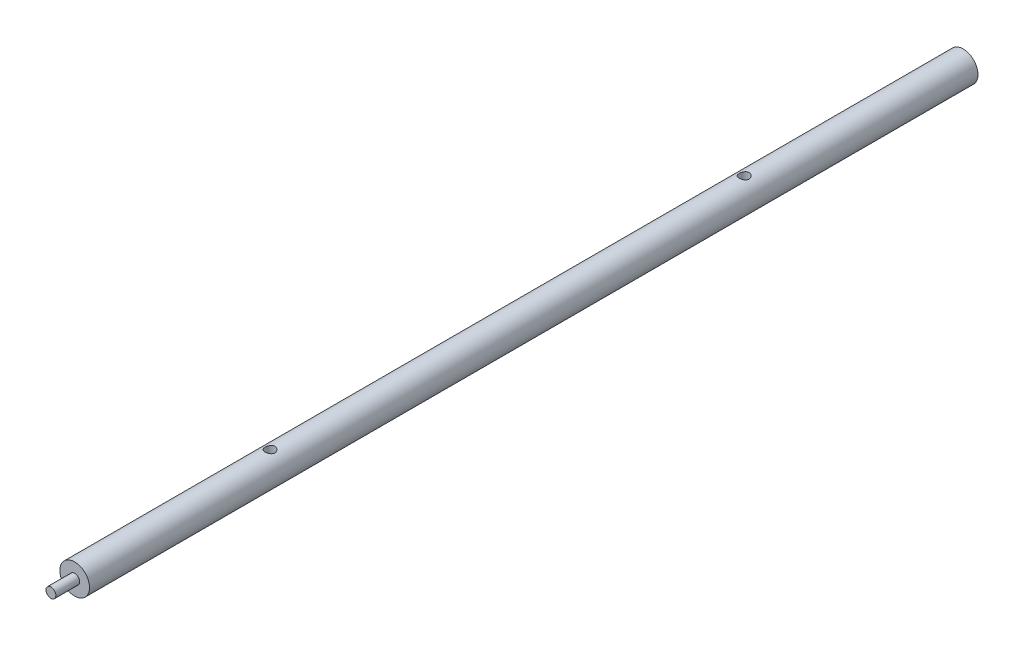
SolidWorks part; units mm, degrees
material "Plain Carbon Steel"
ref_plane "Front Plane" through (0, 0, 0) normal (0, 0, 1) x (1, 0, 0)
ref_plane "Top Plane" through (0, 0, 0) normal (0, 1, 0) x (1, 0, 0)
ref_plane "Right Plane" through (0, 0, 0) normal (1, 0, 0) x (0, 0, -1)
sketch "Sketch1" plane through (0, 0, 0) normal (0, 0, 1) x (1, 0, 0)
  circle A0 centre (0, 0) radius 9.525
  dimension "D1" = 19.05
extrude "Boss-Extrude1" add sketch "Sketch1" along normal blind 586.105
sketch3d "3DSketch1" plane through (0, 0, 0) normal (0, 0, 1) x (1, 0, 0)
ref_axis "Axis1" through (0, 0, 586.105) along (0, 0, -1)
ref_plane "Plane1" through (0, -9.525, 0) normal (0, 1, 0) x (1, 0, 0)
sketch "Sketch3" plane through (0, -9.525, 0) normal (0, 1, 0) x (1, 0, 0)
  line L0 (0, -586.105) -> (0, 0) construction
  line L1 (9.525, 0) -> (-9.525, 0) construction
  line L2 (-9.525, -586.105) -> (9.525, -586.105) construction
  circle A0 centre (0, -445.389) radius 3.175
  circle A1 centre (0, -140.716) radius 3.175
  dimension "D1" = 0
  dimension "D2" = 0
  dimension "D3" = 6.35
  dimension "D4" = 140.716
  dimension "D5" = 6.35
  dimension "D6" = 140.716
extrude "Cut-Extrude2" cut sketch "Sketch3" along normal up to next
sketch "Sketch5" plane through (0, -9.525, 0) normal (0, 1, 0) x (1, 0, 0)
  line L0 (0, -178.816) -> (0, -159.766) construction
  line L1 (-2.3813, -178.816) -> (-2.3813, -159.766)
  line L2 (2.3813, -178.816) -> (2.3813, -159.766)
  line L3 (0, -407.289) -> (0, -426.339) construction
  line L4 (2.3812, -407.289) -> (2.3812, -426.339)
  line L5 (-2.3813, -407.289) -> (-2.3813, -426.339)
  arc A0 (-2.3813, -178.816) -> (2.3813, -178.816) centre (0, -178.816) ccw
  arc A1 (2.3813, -159.766) -> (-2.3813, -159.766) centre (0, -159.766) ccw
  arc A2 (2.3812, -407.289) -> (-2.3813, -407.289) centre (0, -407.289) ccw
  arc A3 (-2.3813, -426.339) -> (2.3812, -426.339) centre (0, -426.339) ccw
  circle A6 centre (0, -140.716) radius 3.175 construction
  circle A7 centre (0, -445.389) radius 3.175 construction
  point P3 (0, -169.291)
  point P10 (0, -416.814)
  dimension "D1" = 2.3813
  dimension "D2" = 2.3813
  dimension "D3" = 19.05
  dimension "D4" = 19.05
  dimension "D5" = 19.05
  dimension "D6" = 19.05
extrude "Cut-Extrude3" cut sketch "Sketch5" along normal blind 2.3813
sketch "Sketch6" plane through (0, 0, 586.105) normal (0, 0, 1) x (1, 0, 0)
  circle A0 centre (0, 0) radius 3.175
  dimension "D1" = 6.35
extrude "Cut-Extrude4" cut sketch "Sketch6" against normal blind 15.24 flip side to cut
